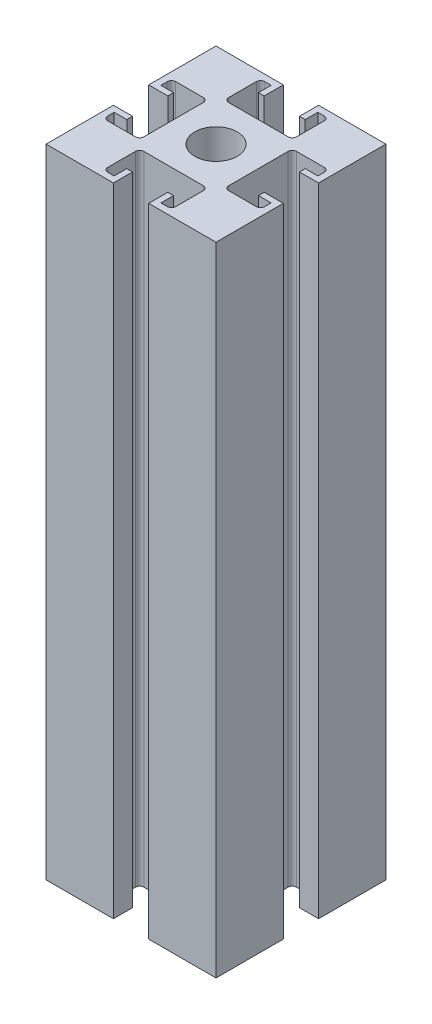
SolidWorks part; units mm, degrees
ref_plane "Plano frontal" through (0, 0, 0) normal (0, 0, 1) x (1, 0, 0)
ref_plane "Plano superior" through (0, 0, 0) normal (0, 1, 0) x (1, 0, 0)
ref_plane "Plano direito" through (0, 0, 0) normal (1, 0, 0) x (0, 0, -1)
sketch "Esboço2" plane through (0, 0, 0) normal (0, 1, 0) x (1, 0, 0)
  line L0 (-1.8037, 6.5679) -> (2.6963, 6.5679)
  line L1 (-1.8037, -17.5821) -> (38.1963, -17.5821)
  line L2 (-1.8037, -17.5821) -> (-1.8037, 22.4179)
  line L3 (-1.8037, 22.4179) -> (38.1963, 22.4179)
  line L4 (38.1963, -17.5821) -> (38.1963, 22.4179)
  line L5 (2.6963, 6.5679) -> (2.6963, 7.9179)
  line L6 (2.2188, 10.4179) -> (7.2188, 10.4179)
  line L7 (8.2188, 9.4179) -> (8.2188, -4.5821)
  line L8 (7.2188, -5.5821) -> (2.2188, -5.5821)
  line L9 (2.2188, -5.5821) -> (0.7188, -5.5821)
  line L10 (2.6963, -1.7321) -> (-1.8037, -1.7321)
  line L11 (0.7188, 10.4179) -> (2.2188, 10.4179)
  line L12 (2.6963, -1.7321) -> (2.6963, -3.0821)
  line L13 (2.6963, 7.9179) -> (-0.2812, 7.9179)
  line L14 (-0.2812, 7.9179) -> (-0.2812, 9.4179)
  line L15 (2.6963, -3.0821) -> (-0.2812, -3.0821)
  line L16 (-0.2812, -3.0821) -> (-0.2812, -4.5821)
  line L17 (-1.8037, 6.5679) -> (-1.8037, -1.7321)
  line L18 (18.1963, 22.4179) -> (18.1963, -17.5821) construction
  line L19 (-1.8037, 2.4179) -> (38.1963, 2.4179) construction
  line L20 (38.1963, 6.5679) -> (38.1963, -1.7321)
  line L21 (36.6737, -3.0821) -> (36.6737, -4.5821)
  line L22 (33.6963, -3.0821) -> (36.6737, -3.0821)
  line L23 (36.6737, 7.9179) -> (36.6737, 9.4179)
  line L24 (33.6963, 7.9179) -> (36.6737, 7.9179)
  line L25 (33.6963, -1.7321) -> (33.6963, -3.0821)
  line L26 (35.6737, 10.4179) -> (34.1737, 10.4179)
  line L27 (33.6963, -1.7321) -> (38.1963, -1.7321)
  line L28 (34.1737, -5.5821) -> (35.6737, -5.5821)
  line L29 (29.1737, -5.5821) -> (34.1737, -5.5821)
  line L30 (28.1737, 9.4179) -> (28.1737, -4.5821)
  line L31 (34.1737, 10.4179) -> (29.1737, 10.4179)
  line L32 (33.6963, 6.5679) -> (33.6963, 7.9179)
  line L33 (38.1963, 6.5679) -> (33.6963, 6.5679)
  arc A0 (0.7188, 10.4179) -> (-0.2812, 9.4179) centre (0.7188, 9.4179) ccw
  arc A1 (0.7188, -5.5821) -> (-0.2812, -4.5821) centre (0.7188, -4.5821) cw
  arc A2 (8.2188, 9.4179) -> (7.2188, 10.4179) centre (7.2188, 9.4179) ccw
  arc A3 (7.2188, -5.5821) -> (8.2188, -4.5821) centre (7.2188, -4.5821) ccw
  arc A4 (29.1737, -5.5821) -> (28.1737, -4.5821) centre (29.1737, -4.5821) cw
  arc A5 (28.1737, 9.4179) -> (29.1737, 10.4179) centre (29.1737, 9.4179) cw
  arc A6 (35.6737, -5.5821) -> (36.6737, -4.5821) centre (35.6737, -4.5821) ccw
  arc A7 (35.6737, 10.4179) -> (36.6737, 9.4179) centre (35.6737, 9.4179) cw
  circle A8 centre (18.1963, 2.4179) radius 5
  point P22 (-0.2812, -5.5821)
  point P25 (8.2188, 10.4179)
  point P28 (8.2188, -5.5821)
  point P29 (-1.8037, 2.4179)
  point P30 (-1.8037, 2.4179)
  point P57 (28.1737, -5.5821)
  point P58 (28.1737, 10.4179)
  point P59 (36.6737, -5.5821)
  point P62 (18.1963, -17.5821)
  line B0 (14.0463, -17.5821) -> (14.0463, -13.0821)
  line B1 (14.0463, -13.0821) -> (12.6963, -13.0821)
  line B2 (10.1963, -13.5595) -> (10.1963, -8.5595)
  line B3 (11.1963, -7.5595) -> (25.1963, -7.5595)
  line B4 (26.1963, -8.5595) -> (26.1963, -13.5595)
  line B5 (26.1963, -13.5595) -> (26.1963, -15.0595)
  line B6 (22.3463, -13.0821) -> (22.3463, -17.5821)
  line B7 (10.1963, -15.0595) -> (10.1963, -13.5595)
  line B8 (22.3463, -13.0821) -> (23.6963, -13.0821)
  line B9 (12.6963, -13.0821) -> (12.6963, -16.0595)
  line B10 (12.6963, -16.0595) -> (11.1963, -16.0595)
  line B11 (23.6963, -13.0821) -> (23.6963, -16.0595)
  line B12 (23.6963, -16.0595) -> (25.1963, -16.0595)
  line B13 (14.0463, -17.5821) -> (22.3463, -17.5821)
  arc B14 (10.1963, -15.0595) -> (11.1963, -16.0595) centre (11.1963, -15.0595) ccw
  arc B15 (26.1963, -15.0595) -> (25.1963, -16.0595) centre (25.1963, -15.0595) cw
  arc B16 (11.1963, -7.5595) -> (10.1963, -8.5595) centre (11.1963, -8.5595) ccw
  arc B17 (26.1963, -8.5595) -> (25.1963, -7.5595) centre (25.1963, -8.5595) ccw
  line B18 (14.0463, 22.4179) -> (14.0463, 17.9179)
  line B19 (14.0463, 17.9179) -> (12.6963, 17.9179)
  line B20 (10.1963, 18.3954) -> (10.1963, 13.3954)
  line B21 (11.1963, 12.3954) -> (25.1963, 12.3954)
  line B22 (26.1963, 13.3954) -> (26.1963, 18.3954)
  line B23 (26.1963, 18.3954) -> (26.1963, 19.8954)
  line B24 (22.3463, 17.9179) -> (22.3463, 22.4179)
  line B25 (10.1963, 19.8954) -> (10.1963, 18.3954)
  line B26 (22.3463, 17.9179) -> (23.6963, 17.9179)
  line B27 (12.6963, 17.9179) -> (12.6963, 20.8954)
  line B28 (12.6963, 20.8954) -> (11.1963, 20.8954)
  line B29 (23.6963, 17.9179) -> (23.6963, 20.8954)
  line B30 (23.6963, 20.8954) -> (25.1963, 20.8954)
  line B31 (14.0463, 22.4179) -> (22.3463, 22.4179)
  arc B32 (10.1963, 19.8954) -> (11.1963, 20.8954) centre (11.1963, 19.8954) cw
  arc B33 (26.1963, 19.8954) -> (25.1963, 20.8954) centre (25.1963, 19.8954) ccw
  arc B34 (11.1963, 12.3954) -> (10.1963, 13.3954) centre (11.1963, 13.3954) cw
  arc B35 (26.1963, 13.3954) -> (25.1963, 12.3954) centre (25.1963, 13.3954) cw
  dimension "D8" = 2.5
  dimension "D10" = 1
  dimension "D11" = 1
  dimension "D12" = 1
  dimension "D13" = 10
  dimension "D1" = 40
  dimension "D2" = 40
  dimension "D3" = 8.3
  dimension "D4" = 6
  dimension "D5" = 4.5
  dimension "D6" = 1.35
  dimension "D7" = 16
  dimension "D9" = 2.5
sketch_block_instance "Bloco1-1"
sketch_block "Bloco1" parameters "D2"=1, "D3"=1, "D1"=2.5
sketch_block_instance "Bloco1-2"
extrude "Ressalto-extrusão1" add sketch "Esboço2" along normal blind 150 contours B22 B35 B21 B34 B20 B25 B32 B28 B27 B19 B18 L3 L2 L0 L5 L13 L14 A0 L11 L6 A2 L7 A3 L8 L9 A1 L16 L15 L12 L10 L1 B0 B1 B9 B10 B14 B7 B2 B16 B3 B17 B4 B5 B15 B12 B11 B8 B6 L4 | A8 region at (-1.238, 0, -14.4929) region at (18.1963, 0, -2.4179)
extrude "Corte-extrusão1" cut sketch "Esboço2<3>" along normal blind 10 contours A8
sketch "Esboço2<3>" plane through (0, 0, 0) normal (0, 1, 0) x (1, 0, 0) same geometry as "Esboço2"
sketch "Esboço4" plane through (0, 150, 0) normal (0, 1, 0) x (1, 0, 0)
  line L0 (8.2188, 2.4179) -> (28.1737, 2.4179) construction
  line L1 (8.2188, 9.4179) -> (8.2188, -4.5821) construction
  line L2 (28.1737, 9.4179) -> (28.1737, -4.5821) construction
  line L3 (11.1963, 12.3954) -> (25.1963, 12.3954) construction
  line L4 (18.1963, 12.3954) -> (18.1963, -7.5595) construction
  line L5 (11.1963, -7.5595) -> (25.1963, -7.5595) construction
  circle A0 centre (18.1963, 2.4179) radius 5
  dimension "D1" = 10
extrude "Corte-extrusão2" cut sketch "Esboço4" against normal blind 20
